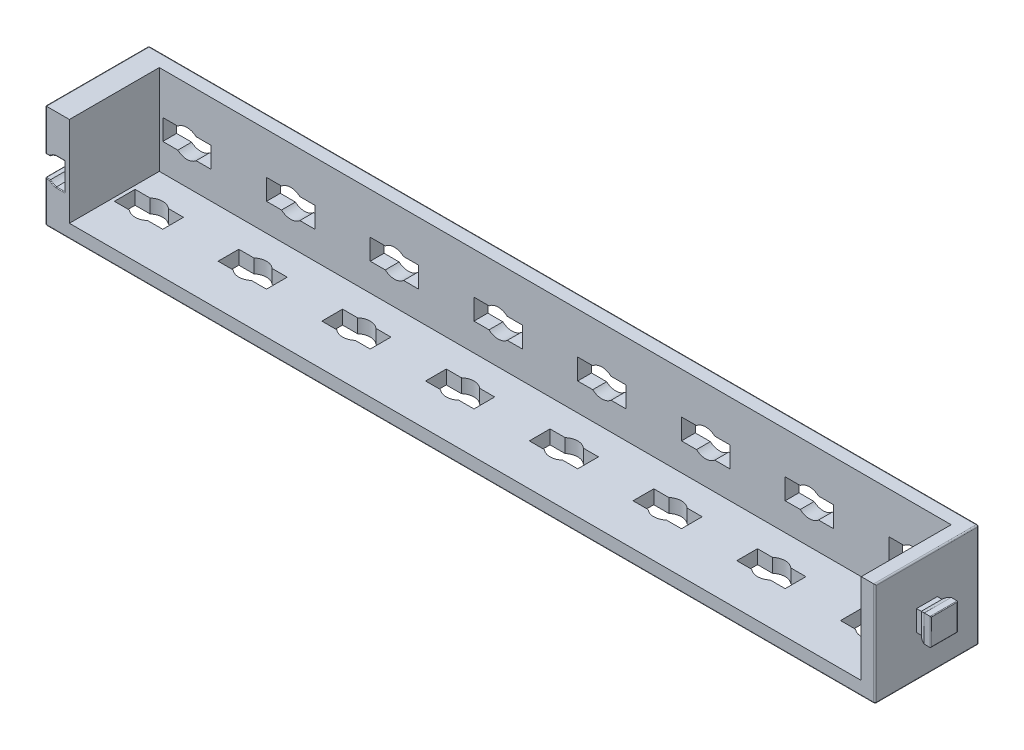
SolidWorks part; units mm, degrees
ref_plane "前视基准面" through (0, 0, 0) normal (0, 0, 1) x (1, 0, 0)
ref_plane "上视基准面" through (0, 0, 0) normal (0, 1, 0) x (1, 0, 0)
ref_plane "右视基准面" through (0, 0, 0) normal (1, 0, 0) x (0, 0, -1)
sketch "草图1" plane through (0, 0, 0) normal (0, 1, 0) x (1, 0, 0)
  line L0 (-60, 7.5) -> (-60, -7.5)
  line L1 (-60, 7.5) -> (60, 7.5)
  line L2 (-60, -7.5) -> (60, -7.5)
  line L3 (60, 7.5) -> (60, -7.5)
  line L4 (-60, 7.5) -> (60, -7.5) construction
  line L5 (-60, -7.5) -> (60, 7.5) construction
  point P1 (0, 0)
  dimension "D1" = 15
  dimension "D2" = 120
extrude "凸台-拉伸1" add sketch "草图1" along normal blind 15
sketch "草图2" plane through (0, 15, 0) normal (0, 1, 0) x (1, 0, 0)
  line L0 (58, -7.5) -> (-56.5, -7.5)
  line L1 (58, -7.5) -> (58, 5.5)
  line L2 (-56.5, -7.5) -> (-56.5, 5.5)
  line L3 (58, 5.5) -> (-56.5, 5.5)
  line L4 (-60, -7.5) -> (60, -7.5) construction
  line L5 (60, 7.5) -> (-60, 7.5) construction
  line L6 (-60, 7.5) -> (-60, -7.5) construction
  dimension "D1" = 2
  dimension "D2" = 2
  dimension "D3" = 3.5
extrude "切除-拉伸1" cut sketch "草图2" against normal blind 13
sketch "草图3" plane through (0, 0, 0) normal (0, 0, 1) x (1, 0, 0)
  line L0 (60, 7.5) -> (62, 7.5) construction
  line L1 (60, 15) -> (60, 0) construction
  line L2 (62, 7.5) -> (62.5, 7.5) construction
  line L3 (60, 6) -> (60, 9)
  line L4 (60, 9) -> (60.6771, 9)
  line L5 (62.5, 5.55) -> (62.5, 9.45)
  line L6 (62.5, 9.45) -> (61.5556, 9.45)
  line L7 (62.5, 5.55) -> (61.5556, 5.55)
  line L8 (60, 6) -> (60.6771, 6)
  arc A0 (61.5556, 9.45) -> (60.6771, 9) centre (62, 7.5) ccw
  arc A1 (61.5556, 5.55) -> (60.6771, 6) centre (62, 7.5) cw
  dimension "D5" = 2
  dimension "D1" = 2
  dimension "D2" = 0.5
  dimension "D3" = 1.5
  dimension "D4" = 1.95
extrude "凸台-拉伸2" add sketch "草图3" along normal blind 2 and the other way blind 2
sketch "草图4" plane through (0, 0, 0) normal (0, 1, 0) x (1, 0, 0)
  line L0 (60, 0) -> (62, 0) construction
  line L1 (60, 2) -> (60, -2) construction
  line L2 (62, 0) -> (62.5, 0) construction
  line L3 (62.5, 2) -> (62.5, -2) construction
  line L4 (60, 0) -> (60, 1.5) construction
  line L5 (60, 1.5) -> (60.6771, 1.5)
  line L6 (62.5, 0) -> (62.5, 1.95) construction
  line L7 (62.5, 1.95) -> (61.5556, 1.95)
  line L8 (60, 1.5) -> (60, 2)
  line L9 (60, 2) -> (62.5, 2)
  line L10 (62.5, 2) -> (62.5, 1.95)
  line L11 (62.5, -1.95) -> (61.5556, -1.95)
  line L12 (60, -1.5) -> (60.6771, -1.5)
  line L13 (60, -1.5) -> (60, -2)
  line L14 (60, -2) -> (62.5, -2)
  line L15 (62.5, -2) -> (62.5, -1.95)
  arc A0 (61.5556, 1.95) -> (60.6771, 1.5) centre (62, 0) ccw
  arc A1 (61.5556, -1.95) -> (60.6771, -1.5) centre (62, 0) cw
  dimension "D4" = 2
  dimension "D1" = 2
  dimension "D2" = 1.5
  dimension "D3" = 1.95
extrude "切除-拉伸2" cut sketch "草图4" along normal through all
sketch "草图5" plane through (0, 0, 7.5) normal (0, 0, 1) x (1, 0, 0)
  line L0 (-60, 7.5) -> (-58, 7.5) construction
  line L1 (-60, 15) -> (-60, 0) construction
  line L2 (-58, 7.5) -> (-57.2, 7.5) construction
  line L3 (-60, 6) -> (-60, 9)
  line L4 (-60, 9) -> (-59.3229, 9)
  line L5 (-57.2, 5.55) -> (-57.2, 9.45)
  line L6 (-57.2, 9.45) -> (-58.4444, 9.45)
  line L7 (-57.2, 5.55) -> (-58.4444, 5.55)
  line L8 (-60, 6) -> (-59.3229, 6)
  arc A0 (-58.4444, 9.45) -> (-59.3229, 9) centre (-58, 7.5) ccw
  arc A1 (-58.4444, 5.55) -> (-59.3229, 6) centre (-58, 7.5) cw
  dimension "D5" = 2
  dimension "D1" = 2
  dimension "D2" = 0.8
  dimension "D3" = 1.5
  dimension "D4" = 1.95
extrude "切除-拉伸3" cut sketch "草图5" against normal blind 10
sketch "草图6" plane through (0, 0, -7.5) normal (0, 0, -1) x (-1, 0, 0)
  line L0 (-60, 7.5) -> (-52.5, 7.5) construction
  line L1 (-60, 15) -> (-60, 0) construction
  line L2 (-49, 9) -> (-49, 6)
  line L3 (-49, 9) -> (-51.1771, 9)
  line L4 (-49, 6) -> (-51.1771, 6)
  line L5 (-56, 9) -> (-56, 6)
  line L6 (-49, 9) -> (-56, 6) construction
  line L7 (-49, 6) -> (-56, 9) construction
  line L8 (-53.8229, 9) -> (-56, 9)
  line L9 (-53.8229, 6) -> (-56, 6)
  arc A0 (-53.8229, 6) -> (-51.1771, 6) centre (-52.5, 7.5) ccw
  arc A1 (-51.1771, 9) -> (-53.8229, 9) centre (-52.5, 7.5) ccw
  dimension "D2" = 4
  dimension "D1" = 7.5
  dimension "D3" = 3
  dimension "D4" = 7
extrude "切除-拉伸4" cut sketch "草图6" against normal up to next
pattern_linear "阵列(线性)1" count 8 spacing 15 along (-1, 0, 0) of "切除-拉伸4"
sketch "草图7" plane through (0, 0, 0) normal (0, -1, 0) x (1, 0, 0)
  line L0 (60, 0) -> (52.5, 0) construction
  line L1 (60, -1.5) -> (60, 1.5) construction
  line L2 (56, 1.5) -> (56, -1.5)
  line L3 (56, 1.5) -> (53.8229, 1.5)
  line L4 (56, -1.5) -> (53.8229, -1.5)
  line L5 (49, 1.5) -> (49, -1.5)
  line L6 (56, 1.5) -> (49, -1.5) construction
  line L7 (56, -1.5) -> (49, 1.5) construction
  line L8 (51.1771, 1.5) -> (49, 1.5)
  line L9 (51.1771, -1.5) -> (49, -1.5)
  arc A0 (51.1771, -1.5) -> (53.8229, -1.5) centre (52.5, 0) ccw
  arc A1 (53.8229, 1.5) -> (51.1771, 1.5) centre (52.5, 0) ccw
  dimension "D2" = 4
  dimension "D1" = 7.5
  dimension "D3" = 3
  dimension "D4" = 7
extrude "切除-拉伸5" cut sketch "草图7" against normal up to next
pattern_linear "阵列(线性)2" count 8 spacing 15 along (-1, 0, 0) of "切除-拉伸5"
fillet "圆角1" radius 0.2 12 edges at (-60, 12, 7.5) (-60, 3, 7.5) (-60, 0, 0) (-60, 7.5, -7.5) (-60, 15, 0) (0, 15, -7.5) (0, 0, -7.5) (0, 0, 7.5) (60, 15, 0) (60, 7.5, 7.5) (60, 7.5, -7.5) (60, 0, 0)
fillet "圆角2" radius 0.1 12 edges at (-60, 6, 2.4) (-59.9414, 6, 7.4414) (-60, 9, 2.4) (-59.9414, 9, 7.4414) (-57.8222, 5.55, 7.5) (-58.9118, 5.72, 7.5) (-59.5614, 6, 7.5) (-59.5614, 9, 7.5) (-58.9118, 9.28, 7.5) (-57.8222, 9.45, 7.5) (-57.2, 7.5, 7.5) (-60, 7.5, -2.5)
fillet "圆角3" radius 0.1 4 edges at (62.5, 7.5, 1.95) (62.5, 9.45, 0) (62.5, 7.5, -1.95) (62.5, 5.55, 0)
